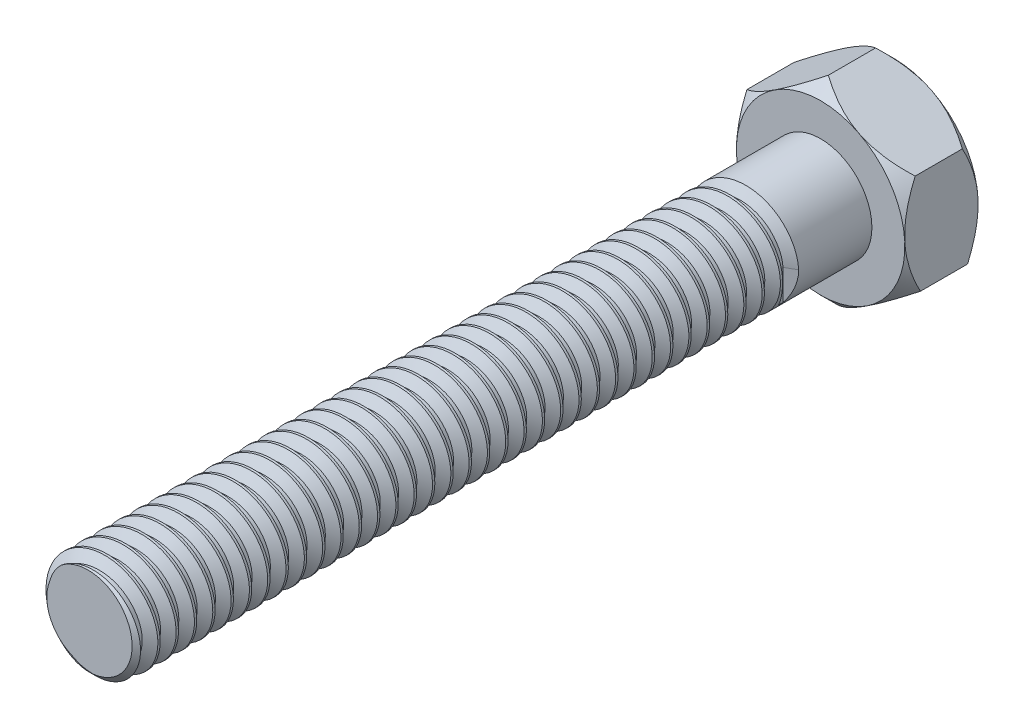
SolidWorks part; units mm, degrees
ref_plane "Front Plane" through (0, 0, 0) normal (0, 0, 1) x (1, 0, 0)
ref_plane "Top Plane" through (0, 0, 0) normal (0, 1, 0) x (1, 0, 0)
ref_plane "Right Plane" through (0, 0, 0) normal (1, 0, 0) x (0, 0, -1)
sketch "Sketch1" plane through (0, 0, 0) normal (0, 0, 1) x (1, 0, 0)
  line L1 (5.9221, -3.0021) -> (5.5609, 3.6276)
  line L2 (5.5609, 3.6276) -> (-0.3612, 6.6297)
  line L3 (-0.3612, 6.6297) -> (-5.9221, 3.0021)
  line L4 (-5.9221, 3.0021) -> (-5.5609, -3.6276)
  line L5 (-5.5609, -3.6276) -> (0.3612, -6.6297)
  line L6 (0.3612, -6.6297) -> (5.9221, -3.0021)
  circle A0 centre (0, 0) radius 5.75 construction
  dimension "D1" = 11.5
extrude "Boss-Extrude1" add sketch "Sketch1" along normal mid plane 5 contours L2 L3 L4 L5 L6 L1
sketch "Sketch2" plane through (0, 0, 2.5) normal (0, 0, 1) x (1, 0, 0)
  circle A0 centre (0, 0) radius 10
sketch "Sketch3" plane through (0, 0, 2.5) normal (0, 0, 1) x (1, 0, 0)
  circle A0 centre (0, 0) radius 3.5
  dimension "D1" = 7
extrude "Boss-Extrude2" add sketch "Sketch3" along normal blind 50
chamfer "Chamfer1" distance 0.5 angle 45 1 edges at (3.5, 0, 52.5)
thread "Thread1" pitch 1.25 method cut profile "Thread Profile1" start angle 0, offset 5, length 45, pitch 1.25, diameter 7
ref_plane "Plane1" through (3.5, 0, 7.5) normal (0, -1, 0) x (1, 0, 0)
sketch "Thread Profile1" plane through (3.5, 0, 7.5) normal (0, -1, 0) x (1, 0, 0)
  line L0 (0, 0) -> (0, 1.25) construction
  line L11 (0, 0) -> (0, 1.0937)
  line L12 (0, 1.0937) -> (-0.6766, 0.7031)
  line L13 (-0.6766, 0.7031) -> (-0.6766, 0.3906)
  line L15 (-0.6766, 0.3906) -> (0, 0)
  line L17 (-0.6766, 0.5469) -> (0, 0.5469) construction
  point P2 (0, 0)
  dimension "Pitch" = 1.25
  dimension "Profile_Angle" = 60
  dimension "Profile_Land" = 0.3125
  dimension "Profile_Height" = 0.6766
sketch "Sketch12" plane through (0, 0, 0) normal (0, 1, 0) x (1, 0, 0)
  line L4 (3.5, -7.5) -> (2.8234, -7.8906)
  line L5 (2.8234, -7.8906) -> (2.8234, -8.2031)
  line L6 (2.8234, -8.2031) -> (3.5, -8.5937)
  line L7 (3.5, -8.5937) -> (3.5, -7.5)
  line L8 (3.5, -7.5) -> (2.8234, -7.8906)
  line L9 (2.8234, -7.8906) -> (2.8234, -8.2031)
  line L10 (2.8234, -8.2031) -> (3.5, -8.5937)
  line L11 (3.5, -8.5937) -> (3.5, -7.5)
  dimension "D1" = 0
extrude "Cut-Extrude2" cut sketch "Sketch12" against normal through all
sketch "Sketch13" plane through (0, 0, -2.5) normal (0, 0, -1) x (-1, 0, 0)
  circle A0 centre (0, 0) radius 5.75
extrude "Cut-Extrude3" cut sketch "Sketch13" against normal mid plane 10 draft 45 flip side to cut
sketch "Sketch14" plane through (0, 0, 2.5) normal (0, 0, 1) x (1, 0, 0)
  circle A0 centre (0, 0) radius 5.75
extrude "Cut-Extrude4" cut sketch "Sketch14" against normal mid plane 10 draft 45 flip side to cut
